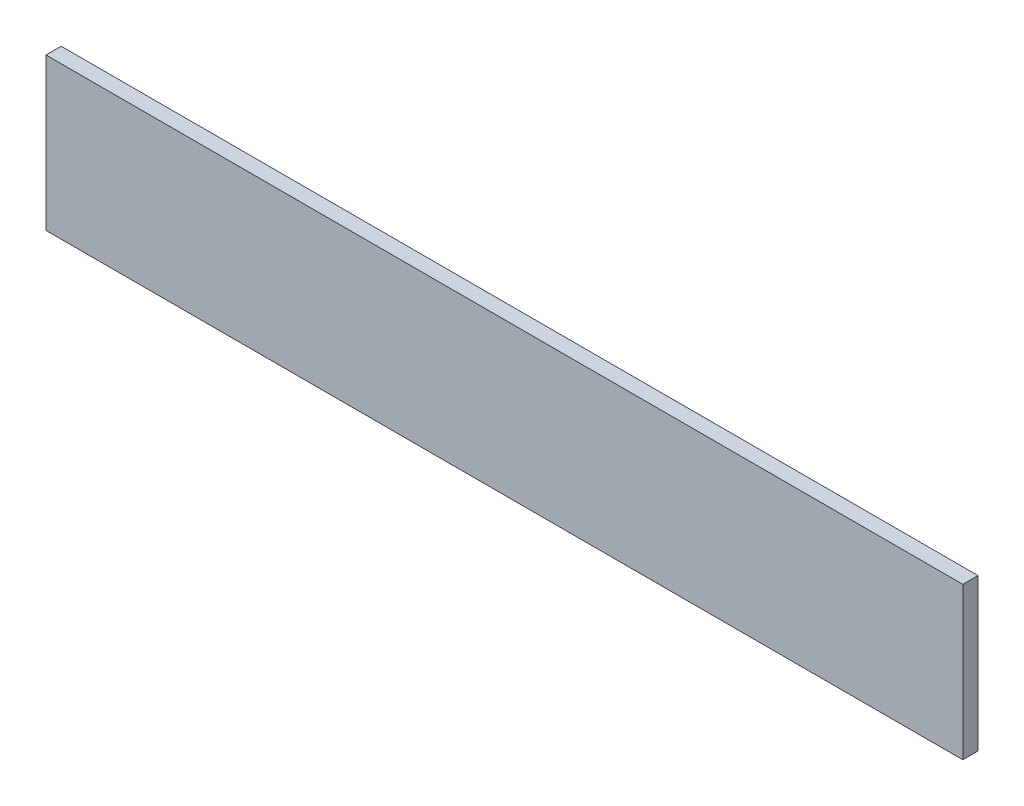
SolidWorks part; units mm, degrees
ref_plane "Front Plane" through (0, 0, 0) normal (0, 0, 1) x (1, 0, 0)
ref_plane "Top Plane" through (0, 0, 0) normal (0, 1, 0) x (1, 0, 0)
ref_plane "Right Plane" through (0, 0, 0) normal (1, 0, 0) x (0, 0, -1)
sketch "Sketch1" plane through (0, 0, 0) normal (0, 0, 1) x (1, 0, 0)
  line L1 (0, 0) -> (181, 0)
  line L2 (0, 0) -> (0, 30)
  line L3 (0, 30) -> (181, 30)
  line L4 (181, 0) -> (181, 30)
  dimension "D1" = 181
  dimension "D2" = 30
extrude "Boss-Extrude1" add sketch "Sketch1" along normal blind 3
